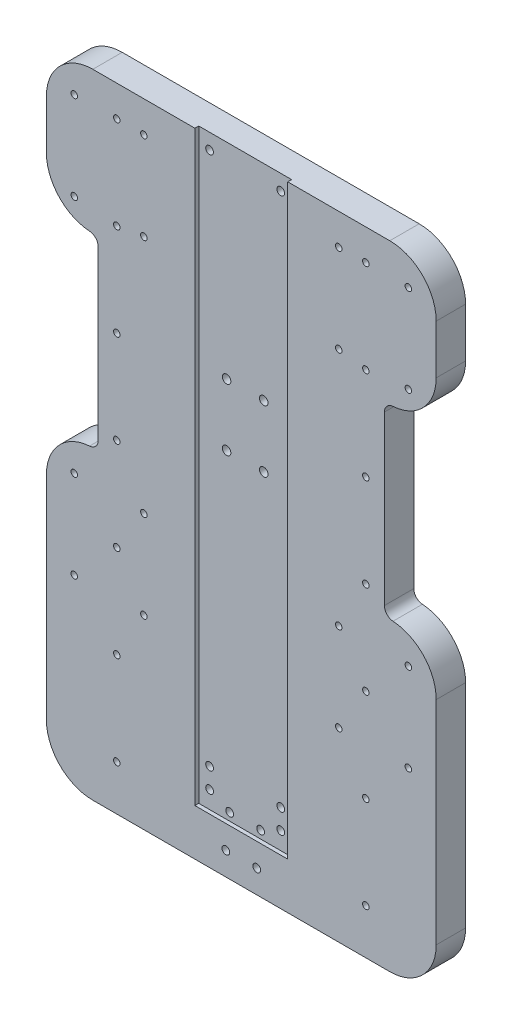
SolidWorks part; units mm, degrees
ref_plane "Piano frontale" through (0, 0, 0) normal (0, 0, 1) x (1, 0, 0)
ref_plane "Piano superiore" through (0, 0, 0) normal (0, 1, 0) x (1, 0, 0)
ref_plane "Piano destro" through (0, 0, 0) normal (1, 0, 0) x (0, 0, -1)
sketch "Schizzo1" plane through (0, 0, 0) normal (0, 0, 1) x (1, 0, 0)
  line L1 (126, -250) -> (-126, -250)
  line L2 (126, -250) -> (126, 250)
  line L3 (126, 250) -> (-126, 250)
  line L4 (-126, -250) -> (-126, 250)
  line L5 (126, -250) -> (-126, 250) construction
  line L6 (126, 250) -> (-126, -250) construction
  point P0 (0, 0)
  dimension "D1" = 252
  dimension "D2" = 500
extrude "Estrusione-Estrusione1" add sketch "Schizzo1" along normal blind 19
sketch "Schizzo2" plane through (0, 0, 19) normal (0, 0, 1) x (1, 0, 0)
  line L0 (1265.2426, 21.4119) -> (-695.7574, 21.4119) construction
  line L1 (1265.2426, 13.5541) -> (-695.7574, 13.5541) construction
  line L2 (1265.2426, 53.5541) -> (-695.7574, 53.5541) construction
  line L3 (1265.2426, 61.4119) -> (-695.7574, 61.4119) construction
  line L4 (-126, 250) -> (-126, -250)
  line L5 (-126, -250) -> (126, -250)
  line L6 (126, -250) -> (126, 250)
  line L7 (126, 250) -> (-126, 250)
  line L8 (-126, 250) -> (-126, -250) construction
  line L9 (-126, -250) -> (126, -250) construction
  line L10 (126, -250) -> (126, 250) construction
  line L11 (126, 250) -> (-126, 250) construction
  line L12 (1265.2426, 21.4119) -> (-695.7574, 21.4119) construction
  line L13 (1265.2426, 13.5541) -> (-695.7574, 13.5541) construction
  line L14 (1265.2426, 53.5541) -> (-695.7574, 53.5541) construction
  line L15 (1265.2426, 61.4119) -> (-695.7574, 61.4119) construction
  line L16 (126, -45.017) -> (-126, -45.017) construction
  line L17 (126, -25.017) -> (-126, -25.017) construction
  line L18 (126, -45.017) -> (-126, -45.017) construction
  line L19 (126, -25.017) -> (-126, -25.017) construction
  line L20 (-126, -45.017) -> (-126, -25.017) construction
  line L21 (126, -35.017) -> (-126, -35.017) construction
  line L22 (-126, -45.017) -> (126, -45.017) construction
  line L23 (-126, -45.017) -> (-126, -25.017) construction
  line L24 (-126, -25.017) -> (126, -25.017) construction
  line L25 (126, -45.017) -> (126, -25.017) construction
  circle A0 centre (110, 17.483) radius 3.9289
  circle A1 centre (110, 57.483) radius 3.9289
  circle A2 centre (-110, 17.483) radius 3.9289
  circle A3 centre (-110, 57.483) radius 3.9289
  circle A4 centre (110, -35.017) radius 3.5
  circle A5 centre (-110, -35.017) radius 3.5
  circle A6 centre (55, -35.017) radius 3.5
  circle A8 centre (-55, -35.017) radius 3.5
  circle A9 centre (20, -35.017) radius 3.5
  circle A10 centre (-20, -35.017) radius 3.5
  circle A11 centre (165, -35.017) radius 3.5 [skipped]
  dimension "D2" = 16
  dimension "D3" = 7.8579
  dimension "D4" = 16
  dimension "D5" = 7.8579
  dimension "D6" = 7
  dimension "D7" = 7
  dimension "D8" = 2
  dimension "D1" = 0
  dimension "D9" = 2
  dimension "D10" = 2
  dimension "D11" = 2
sketch "Schizzo3" plane through (0, 250, 0) normal (0, 1, 0) x (1, 0, 0)
  line L0 (126, -19) -> (-126, -19) construction
  line L1 (30, -16.5) -> (-30, -16.5)
  line L2 (30, -16.5) -> (30, -19)
  line L3 (30, -19) -> (-30, -19)
  line L4 (-30, -16.5) -> (-30, -19)
  line L5 (126, -19) -> (126, 0) construction
  line L6 (-126, -19) -> (-126, 0) construction
  line L7 (126, -19) -> (-126, -19) construction
  dimension "D1" = 2.5
  dimension "D2" = 96
  dimension "D3" = 96
extrude "Taglio-Estrusione1" cut sketch "Schizzo3" against normal through all
sketch "Schizzo4" plane through (0, 0, 16.5) normal (0, 0, 1) x (1, 0, 0)
  line L0 (30, -250) -> (30, 250) construction
  line L2 (30, 250) -> (-30, 250) construction
  line L3 (30, -250) -> (30, 250) construction
  line L6 (-30, 250) -> (-126, 250) construction
  line L7 (-30, -250) -> (-30, 250) construction
  point P11 (23, -118)
  point P14 (-23, -118)
  point P15 (-23, -105)
  point P16 (23, -105)
  point P17 (23, 240)
  point P18 (-23, 240)
  dimension "D1" = 46
  dimension "D2" = 13
  dimension "D3" = 13
  dimension "D4" = 46
  dimension "D5" = 7
  dimension "D6" = 345
  dimension "D7" = 10
  dimension "D8" = 46
  dimension "D9" = 7
  dimension "D10" = 10
  dimension "D11" = 7
  dimension "D12" = 7
sketch "Schizzo5" plane through (0, 0, 19) normal (0, 0, 1) x (1, 0, 0)
  point P4 (80.5006, 170)
  point P7 (80.5006, 110)
  point P16 (80.5006, 50)
  point P17 (80.5006, -10)
  point P18 (80.5006, -70)
  point P19 (80.5006, -130)
  point P20 (80.5006, 230)
hole_wizard "Tap Drill for M5 Tap2" positions "Sketch7" profile "Sketch8" hole size "M5" standard "ISO"
sketch "Sketch7" plane through (0, 0, 19) normal (0, 0, 1) x (1, 0, 0)
  point P0 (80.5006, -130)
  point P3 (80.5006, -70)
  point P7 (80.5006, -10)
  point P10 (80.5006, 50)
  point P13 (80.5006, 110)
  point P16 (80.5006, 170)
  point P19 (80.5006, 230)
sketch "Sketch8" plane through (80.5006, -130, 19) normal (1, 0, 0) x (0, -1, 0)
  line L0 (0, 0) -> (0, 37.8618)
  line L1 (0, 37.8618) -> (2.1, 36.6)
  line L2 (2.1, 36.6) -> (2.1, 0)
  line L5 (2.1, 0) -> (0, 0)
  line L10 (0, 37.8618) -> (-2.1, 36.6) construction
  line L11 (0, -6.35) -> (0, 107.95) construction
  dimension "Hole Dia." = 4.2
  dimension "Hole Depth" = 36.6
  dimension "Drill Angle" = 118
sketch "Schizzo6" plane through (0, 0, 19) normal (0, 0, 1) x (1, 0, 0)
  line L0 (126, -250) -> (126, 250) construction
  line L2 (126, 250) -> (30, 250) construction
  point P23 (108, 172.8083)
  point P26 (63, 172.8083)
  point P27 (63, 229.8083)
  point P28 (108, 229.8083)
  dimension "D1" = 45
  dimension "D2" = 45
  dimension "D3" = 57
  dimension "D4" = 57
  dimension "D5" = 18
  dimension "D6" = 20.1917
  dimension "D7" = 20.1917
  dimension "D8" = 18
hole_wizard "Tap Drill for M5 Tap1" positions "Sketch14" profile "Sketch15" hole size "M5" standard "ISO"
sketch "Sketch14" plane through (0, 0, 19) normal (0, 0, 1) x (1, 0, 0)
  point P0 (108, 172.8083)
  point P3 (108, 229.8083)
  point P6 (63, 229.8083)
  point P9 (63, 172.8083)
  point P12 (63, 17.8083)
  point P14 (63, -39.1917)
  point P16 (108, -39.1917)
  point P18 (108, 17.8083)
sketch "Sketch15" plane through (108, 172.8083, 19) normal (1, 0, 0) x (0, -1, 0)
  line L0 (0, 0) -> (0, 37.8618)
  line L1 (0, 37.8618) -> (2.1, 36.6)
  line L2 (2.1, 36.6) -> (2.1, 0)
  line L5 (2.1, 0) -> (0, 0)
  line L10 (0, 37.8618) -> (-2.1, 36.6) construction
  line L11 (0, -6.35) -> (0, 107.95) construction
  dimension "Hole Dia." = 4.2
  dimension "Hole Depth" = 36.6
  dimension "Drill Angle" = 118
hole_wizard "Tap Drill for M6 Tap4" positions "Sketch9" profile "Sketch10" hole size "M6" standard "ISO"
sketch "Sketch9" plane through (0, 0, 16.5) normal (0, 0, 1) x (1, 0, 0)
  point P0 (23, -118)
  point P3 (23, -105)
  point P6 (-23, -118)
  point P9 (-23, -105)
  point P12 (23, 240)
  point P15 (-23, 240)
sketch "Sketch10" plane through (23, -118, 16.5) normal (1, 0, 0) x (0, -1, 0)
  line L0 (0, 0) -> (0, 38.1022)
  line L1 (0, 38.1022) -> (2.5, 36.6)
  line L2 (2.5, 36.6) -> (2.5, 0)
  line L5 (2.5, 0) -> (0, 0)
  line L10 (0, 38.1022) -> (-2.5, 36.6) construction
  line L11 (0, -6.35) -> (0, 107.95) construction
  dimension "Hole Dia." = 5
  dimension "Hole Depth" = 36.6
  dimension "Drill Angle" = 118
sketch "Sketch11" plane through (0, 0, 16.5) normal (0, 0, 1) x (1, 0, 0)
  line L0 (0, -250) -> (0, 250) construction
  line L1 (30, -250) -> (-30, -250) construction
  line L2 (30, 250) -> (-30, 250) construction
ref_plane "Plane1" through (0, 0, 0) normal (-1, 0, 0) x (0, 0, 1)
mirror "Mirror1" about plane through (0, 0, 0) normal (-1, 0, 0) of "Tap Drill for M5 Tap2"
mirror "Mirror2" about plane through (0, 0, 0) normal (-1, 0, 0) of "Tap Drill for M5 Tap1"
sketch "Sketch16" plane through (0, 0, 0) normal (0, 0, -1) x (-1, 0, 0)
  line L0 (126, 250) -> (126, -250) construction
  line L1 (126, -317.9299) -> (-126, -317.9299)
  line L2 (126, -317.9299) -> (126, -159.25)
  line L3 (126, -159.25) -> (-126, -159.25)
  line L4 (-126, -317.9299) -> (-126, -159.25)
  line L5 (-126, -250) -> (-126, 250) construction
  line L9 (-12.9, -159.25) -> (25.2, -159.25) construction
extrude "Cut-Extrude1" cut sketch "Sketch16" against normal blind 28
sketch "Sketch26" plane through (0, 0, 16.5) normal (0, 0, 1) x (1, 0, 0)
  line L0 (30, -159.25) -> (30, 250) construction
  line L1 (-30, -159.25) -> (30, -159.25)
  line L2 (-30, -159.25) -> (-30, -129.25)
  line L3 (-30, -129.25) -> (30, -129.25)
  line L4 (30, -159.25) -> (30, -129.25)
  dimension "D1" = 30
extrude "Boss-Extrude1" add sketch "Sketch26" along normal up to surface (2.5 mm away) up to face at (-78, 45.375, 19)
hole_wizard "M5 Clearance Hole1" positions "Sketch17" profile "Sketch18" hole size "M5" standard "ISO" end condition through all
sketch "Sketch17" plane through (0, 0, 16.5) normal (0, 0, 1) x (1, 0, 0)
  line L0 (12, 77.3083) -> (-12, 117.3083) construction
  line L1 (-12, 117.3083) -> (-12, 77.3083) construction
  line L2 (-12, 77.3083) -> (12, 117.3083) construction
  line L3 (12, 117.3083) -> (12, 77.3083) construction
  line L4 (12, 77.3083) -> (-12, 77.3083) construction
  line L7 (-12, 117.3083) -> (12, 117.3083) construction
  point P0 (-12, 77.3083)
  point P2 (12, 77.3083)
  point P4 (12, 117.3083)
  point P6 (-12, 117.3083)
  dimension "D1" = 40
  dimension "D2" = 24
sketch "Sketch18" plane through (-12, 77.3083, 16.5) normal (1, 0, 0) x (0, -1, 0)
  line L0 (0, 0) -> (0, 16.5)
  line L1 (0, 16.5) -> (2.75, 16.5)
  line L2 (2.75, 16.5) -> (2.75, 0)
  line L5 (2.75, 0) -> (0, 0)
  line L11 (0, -6.35) -> (0, 107.95) construction
  dimension "Thru Hole Dia." = 5.5
  dimension "Thru Hole Depth" = 16.5
sketch "Sketch19" plane through (0, -195.45, 0) normal (0, -1, 0) x (-1, 0, 0)
  line L0 (0, -70.7) -> (0, 68.239) construction
  line L1 (126, -9.5) -> (-126, -9.5) construction
  line L2 (126, -19) -> (126, 0) construction
  line L3 (-126, -19) -> (-126, 0) construction
  line L5 (28.2, 0) -> (-28.2, 0) construction
  point P8 (20, -9.5)
  point P9 (-20, -9.5)
  point P12 (-20, 9.5)
  point P13 (20, 9.5)
  dimension "D1" = 20
hole_wizard "Tap Drill for M6 Tap2" positions "Sketch22" profile "Sketch23" hole size "M6" standard "ISO"
sketch "Sketch22" plane through (0, -159.25, 0) normal (0, -1, 0) x (-1, 0, 0)
  point P0 (20, -7.125)
  point P2 (-20, -7.125)
sketch "Sketch23" plane through (-20, -159.25, 7.125) normal (1, 0, 0) x (0, 0, -1)
  line L0 (0, 0) -> (0, 31.5022)
  line L1 (0, 31.5022) -> (2.5, 30)
  line L2 (2.5, 30) -> (2.5, 0)
  line L5 (2.5, 0) -> (0, 0)
  line L10 (0, 31.5022) -> (-2.5, 30) construction
  line L11 (0, -6.35) -> (0, 107.95) construction
  dimension "Hole Dia." = 5
  dimension "Hole Depth" = 30
  dimension "Drill Angle" = 118
hole_wizard "Tap Drill for M6 Tap3" positions "Sketch24" profile "Sketch25" hole size "M6" standard "ISO" end condition through all
sketch "Sketch24" plane through (0, 0, 0) normal (0, 0, -1) x (-1, 0, 0)
  point P0 (-10, -144.25)
  point P2 (-10, -124.25)
  point P4 (10, -124.25)
  point P6 (10, -144.25)
sketch "Sketch25" plane through (10, -144.25, 0) normal (1, 0, 0) x (0, 1, 0)
  line L0 (0, 0) -> (0, 19)
  line L1 (0, 19) -> (2.5, 19)
  line L2 (2.5, 19) -> (2.5, 0)
  line L5 (2.5, 0) -> (0, 0)
  line L11 (0, -6.35) -> (0, 107.95) construction
  dimension "Thru Hole Dia." = 5
  dimension "Thru Hole Depth" = 19
sketch "Sketch27" plane through (0, 0, 19) normal (0, 0, 1) x (1, 0, 0)
  line L2 (-126, 38.082) -> (-126, 158.222)
  line L4 (-92.5, 38.082) -> (-92.5, 158.222)
  line L5 (-126, 38.082) -> (-92.5, 38.082)
  line L7 (-126, 158.222) -> (-92.5, 158.222)
  line L9 (-92.5, 40.082) -> (-92.5, 156.222) construction
  line L10 (-126, 40.082) -> (-126, 156.222) construction
  line L11 (-128, 158.222) -> (-90.5, 158.222) construction
  line L12 (-128, 38.082) -> (-128, 158.222) construction
  line L13 (-128, 38.082) -> (-90.5, 38.082) construction
  line L14 (-126, 40.082) -> (-92.5, 40.082) construction
  line L15 (-90.5, 38.082) -> (-90.5, 158.222) construction
  line L16 (-126, 156.222) -> (-92.5, 156.222) construction
  line L17 (-126, 98.152) -> (126, 98.152) construction
  line L18 (126, -159.25) -> (126, 250) construction
  line L19 (126, 98.152) -> (0, 98.152) construction
  line L20 (0, 98.152) -> (0, 87.9155) construction
  line L21 (-126, 38.082) -> (-92.5, 38.082)
  line L22 (-126, 158.222) -> (-92.5, 158.222)
  line L23 (126, 158.222) -> (92.5, 158.222)
  line L24 (126, 38.082) -> (92.5, 38.082)
  line L25 (126, 158.222) -> (92.5, 158.222)
  line L26 (126, 38.082) -> (92.5, 38.082)
  line L27 (92.5, 38.082) -> (92.5, 158.222)
  line L28 (126, 38.082) -> (126, 158.222)
  line M11 (-126, 250) -> (-126, -159.25)
  line M13 (126, -159.25) -> (126, 250)
  dimension "D1" = 2
extrude "Cut-Extrude2" cut sketch "Sketch27" against normal blind 76.9911 contours L27 L24 L23 M13 | L7 L5 L4 M11 region at (-109.25, 98.152, 19) region at (109.25, 98.152, 19)
fillet "Fillet1" radius 30 4 edges at (126, 158.222, 9.5) (126, 38.082, 9.5) (-126, 158.222, 9.5) (-126, 38.082, 9.5)
fillet "Fillet2" radius 30 4 edges at (126, 250, 9.5) (-126, 250, 9.5) (-126, -159.25, 9.5) (126, -159.25, 9.5)
fillet "Fillet3" radius 6 4 edges at (92.5, 158.222, 9.5) (92.5, 38.082, 9.5) (-92.5, 38.082, 9.5) (-92.5, 158.222, 9.5)
equation "\"D3@Schizzo3\"=\"D2@Schizzo3\""
equation "\"D11@Schizzo4\"=\"D5@Schizzo4\""
